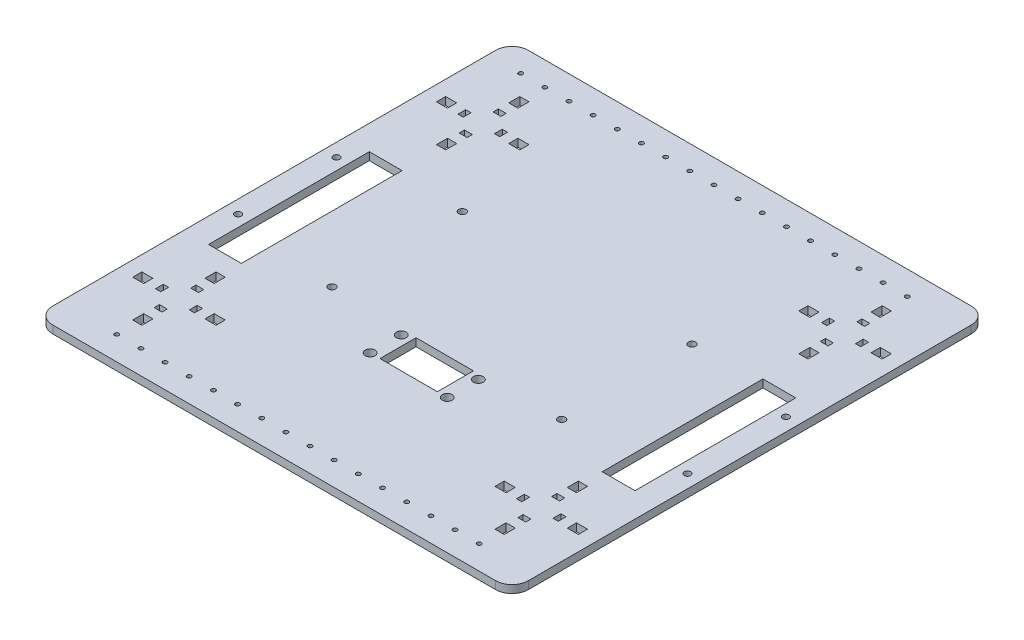
SolidWorks part; units mm, degrees
ref_plane "Front Plane" through (0, 0, 0) normal (0, 0, 1) x (1, 0, 0)
ref_plane "Top Plane" through (0, 0, 0) normal (0, 1, 0) x (1, 0, 0)
ref_plane "Right Plane" through (0, 0, 0) normal (1, 0, 0) x (0, 0, -1)
sketch "Sketch1" plane through (0, 0, 0) normal (0, 1, 0) x (1, 0, 0)
  line L0 (-145, 130.5) -> (145, 130.5) construction
  line L1 (145, -145) -> (-145, -145)
  line L2 (145, -145) -> (145, 145)
  line L3 (145, 145) -> (-145, 145)
  line L4 (-145, -145) -> (-145, 145)
  line L5 (145, -145) -> (-145, 145) construction
  line L6 (145, 145) -> (-145, -145) construction
  line L7 (-145, 116) -> (145, 116) construction
  line L8 (-145, 101.5) -> (145, 101.5) construction
  line L9 (-145, 87) -> (145, 87) construction
  line L10 (-145, 72.5) -> (145, 72.5) construction
  line L11 (-145, 58) -> (145, 58) construction
  line L12 (-145, 43.5) -> (145, 43.5) construction
  line L13 (-145, 29) -> (145, 29) construction
  line L14 (-145, 14.5) -> (145, 14.5) construction
  line L15 (-145, 0) -> (145, 0) construction
  line L16 (-145, -14.5) -> (145, -14.5) construction
  line L17 (-145, -29) -> (145, -29) construction
  line L18 (-145, -43.5) -> (145, -43.5) construction
  line L19 (-145, -58) -> (145, -58) construction
  line L20 (-145, -72.5) -> (145, -72.5) construction
  line L21 (-145, -87) -> (145, -87) construction
  line L22 (-145, -101.5) -> (145, -101.5) construction
  line L23 (-145, -116) -> (145, -116) construction
  line L24 (-145, -130.5) -> (145, -130.5) construction
  line L25 (-145, -145) -> (145, -145) construction
  point P0 (0, 0)
  dimension "D1" = 290
  dimension "D2" = 290
  dimension "D3" = 14.5
  dimension "D5" = 14.5
  dimension "D4" = 20
extrude "Base Plate" add sketch "Sketch1" along normal blind 4.7625
hole_wizard "Caster Holes" positions "Sketch2" profile "Sketch3" hole size "M2" standard "ANSI Metric" end condition through all
sketch "Sketch2" plane through (0, 4.7625, 0) normal (0, 1, 0) x (1, 0, 0)
  line L5 (0, -145) -> (0, 145) construction
  line L6 (145, 145) -> (-145, 145) construction
  line L8 (-145, 0) -> (145, 0) construction
  line L9 (-145, 0) -> (145, 0) construction
  line L10 (-145, 130.5) -> (145, 130.5) construction
  point P200 (-7.366, 130.5)
  point P217 (-22.098, 130.5)
  point P218 (-36.83, 130.5)
  point P219 (-51.562, 130.5)
  point P220 (-66.294, 130.5)
  point P221 (-81.026, 130.5)
  point P222 (-95.758, 130.5)
  point P223 (-110.49, 130.5)
  point P224 (110.49, 130.5)
  point P225 (95.758, 130.5)
  point P226 (81.026, 130.5)
  point P227 (66.294, 130.5)
  point P228 (51.562, 130.5)
  point P229 (36.83, 130.5)
  point P230 (22.098, 130.5)
  point P231 (7.366, 130.5)
  point P232 (7.366, -130.5)
  point P233 (22.098, -130.5)
  point P234 (36.83, -130.5)
  point P235 (51.562, -130.5)
  point P236 (66.294, -130.5)
  point P237 (81.026, -130.5)
  point P238 (95.758, -130.5)
  point P239 (110.49, -130.5)
  point P240 (-110.49, -130.5)
  point P241 (-95.758, -130.5)
  point P242 (-81.026, -130.5)
  point P243 (-66.294, -130.5)
  point P244 (-51.562, -130.5)
  point P245 (-36.83, -130.5)
  point P246 (-22.098, -130.5)
  point P247 (-7.366, -130.5)
  point P250 (-125.222, 130.5)
  dimension "D1" = 7.366
  dimension "D3" = 14.732
  dimension "D2" = 9
sketch "Sketch3" plane through (-125.222, 4.7625, -130.5) normal (1, 0, 0) x (0, 0, 1)
  line L0 (0, 0) -> (0, 4.7625)
  line L1 (0, 4.7625) -> (1.3, 4.7625)
  line L2 (1.3, 4.7625) -> (1.3, 0)
  line L5 (1.3, 0) -> (0, 0)
  line L11 (0, -6.35) -> (0, 107.95) construction
  dimension "Thru Hole Dia." = 2.6
  dimension "Thru Hole Depth" = 4.7625
fillet "Fillet1" radius 10 4 edges at (145, 2.3813, 145) (-145, 2.3813, 145) (145, 2.3813, -145) (-145, 2.3813, -145)
sketch "Sketch4" plane through (0, 0, 0) normal (0, -1, 0) x (1, 0, 0)
  line L0 (145, 0) -> (-145, 0) construction
  line L1 (-145, -135) -> (-145, 135) construction
  line L2 (0, -145) -> (0, 145) construction
  line L3 (-135, 145) -> (135, 145) construction
  point P6 (0, 0)
  point P12 (0, 0)
sketch "Sketch5" plane through (0, 4.7625, 0) normal (0, 1, 0) x (1, 0, 0)
  line L0 (0, 145) -> (0, -145) construction
  line L1 (145, 0) -> (-145, 0) construction
  line L2 (0, 145) -> (0, -145) construction
  line L3 (-17.5, -63) -> (-17.5, -41)
  line L4 (-17.5, -13) -> (17.5, -13) construction
  line L5 (-17.5, -13) -> (-17.5, 9) construction
  line L6 (-17.5, 9) -> (17.5, 9) construction
  line L7 (17.5, -13) -> (17.5, 9) construction
  line L8 (-17.5, -13) -> (17.5, 9) construction
  line L9 (-17.5, 9) -> (17.5, -13) construction
  line L10 (-17.5, -63) -> (17.5, -63)
  line L11 (17.5, -63) -> (17.5, -41)
  line L12 (-17.5, -41) -> (17.5, -41)
  circle A0 centre (-23.5, 6) radius 3 construction
  circle A2 centre (-23.5, -13) radius 3 construction
  circle A3 centre (23.5, 6) radius 3 construction
  circle A4 centre (23.5, -13) radius 3 construction
  circle A5 centre (-23.5, -44) radius 3
  circle A6 centre (-23.5, -63) radius 3
  circle A7 centre (23.5, -63) radius 3
  circle A8 centre (23.5, -44) radius 3
  point P2 (0, -41)
  point P13 (0, -2)
  dimension "D1" = 6
  dimension "D2" = 23.5
  dimension "D3" = 6
  dimension "D4" = 19
  dimension "D5" = 6
  dimension "D6" = 6
  dimension "D8" = 28
  dimension "D7" = 2
extrude "Reflect Holes" cut sketch "Sketch5" against normal up to surface (4.7625 mm away) up to face at (-7.366, 0, -129.2)
sketch "Sketch6" plane through (0, 4.7625, 0) normal (0, 1, 0) x (1, 0, 0)
  line L0 (-137, 145) -> (-137, -145) construction
  line L1 (135, 145) -> (-135, 145) construction
  line L2 (-135, -145) -> (135, -145) construction
  line L3 (-145, 135) -> (-145, -135) construction
  line L16 (145, 0) -> (-145, 0) construction
  line L17 (0, -145) -> (0, 145) construction
  circle A2 centre (-137, 30) radius 2
  circle A22 centre (-137, -30) radius 2
  circle A23 centre (-70, 39.748) radius 2.25
  circle A25 centre (-70, -39.748) radius 2.25
  circle A26 centre (70, -39.748) radius 2.25
  circle A27 centre (70, 39.748) radius 2.25
  circle A28 centre (137, -30) radius 2
  circle A29 centre (137, 30) radius 2
  point P44 (0, 0)
  point P46 (0, 0)
  dimension "D3" = 4
  dimension "D6" = 70
  dimension "D4" = 4.5
  dimension "D1" = 8
  dimension "D2" = 30
  dimension "D5" = 39.748
extrude "bearing slots" cut sketch "Sketch6" against normal up to surface (4.7625 mm away) up to face at (23.5, 0, 47)
sketch "Sketch7" plane through (0, 4.7625, 0) normal (0, 1, 0) x (1, 0, 0)
  line L0 (-145, 135) -> (-145, -135) construction
  line L9 (-130, 43) -> (-110, 43)
  line L10 (-130, 43) -> (-130, -55)
  line L11 (-130, -55) -> (-110, -55)
  line L12 (-110, 43) -> (-110, -55)
  point P9 (-110, -6)
  dimension "D2" = 98
  dimension "D1" = 20
  dimension "D3" = 15
  dimension "D4" = 6
extrude "wheel slots" cut sketch "Sketch7" against normal up to surface (4.7625 mm away) up to face at (-137, 0, 32)
sketch "Sketch9" plane through (0, 4.7625, 0) normal (0, 1, 0) x (1, 0, 0)
  line L0 (-109, -145) -> (-109, 145) construction
  line L1 (135, 145) -> (-135, 145) construction
  line L2 (-145, 135) -> (-145, -135) construction
  line L3 (-135, -145) -> (135, -145) construction
  line L4 (90, -145) -> (90, 145) construction
  line L5 (145, -135) -> (145, 135) construction
  point P0 (-109, -75)
  point P1 (-109, -115)
  point P2 (90, -95)
  point P8 (-109, 0)
  point P21 (90, 0)
  dimension "D1" = 36
  dimension "D2" = 70
  dimension "D3" = 30
  dimension "D4" = 55
  dimension "D5" = 50
sketch "Sketch13" plane through (0, 4.7625, 0) normal (0, 1, 0) x (1, 0, 0)
  line L0 (0, -145) -> (0, 145) construction
  line L7 (135, 145) -> (-135, 145) construction
  line L17 (145, 0) -> (-145, 0) construction
  line L18 (-145, 135) -> (-145, -135) construction
  point P12 (0, 0)
  point P32 (0, 0)
  point P44 (0.04, 0)
mirror "Mirror1" about plane through (0, 0, 0) normal (1, 0, 0) of "wheel slots"
sketch "Sketch15" plane through (0, 4.7625, 0) normal (0, 1, 0) x (1, 0, 0)
  line L21 (-113.25, 118) -> (-107.662, 118)
  line L22 (-113.25, 118) -> (-113.25, 111.269)
  line L23 (-113.25, 111.269) -> (-107.662, 111.269)
  line L24 (-107.662, 118) -> (-107.662, 111.269)
  line L25 (135, 145) -> (-135, 145) construction
  line L26 (-85.056, 95.394) -> (-91.787, 95.394)
  line L27 (-85.056, 95.394) -> (-85.056, 89.806)
  line L28 (-85.056, 89.806) -> (-91.787, 89.806)
  line L29 (-91.787, 95.394) -> (-91.787, 89.806)
  line L30 (-107.662, 67.2) -> (-107.662, 73.931)
  line L31 (-107.662, 67.2) -> (-113.25, 67.2)
  line L32 (-113.25, 67.2) -> (-113.25, 73.931)
  line L33 (-107.662, 73.931) -> (-113.25, 73.931)
  line L34 (-135.856, 89.806) -> (-129.125, 89.806)
  line L35 (-135.856, 89.806) -> (-135.856, 95.394)
  line L36 (-135.856, 95.394) -> (-129.125, 95.394)
  line L37 (-129.125, 89.806) -> (-129.125, 95.394)
  line L38 (-145, 135) -> (-145, -135) construction
  line L39 (-108.4875, 104.925) -> (-113.25, 104.925)
  line L40 (-122.781, 94.5685) -> (-119.581, 94.5685)
  line L41 (-122.781, 94.5685) -> (-122.781, 89.806)
  line L42 (-122.781, 89.806) -> (-119.581, 89.806)
  line L43 (-119.581, 94.5685) -> (-119.581, 89.806)
  line L44 (-108.4875, 104.925) -> (-108.4875, 101.725)
  line L45 (-108.4875, 101.725) -> (-113.25, 101.725)
  line L46 (-113.25, 104.925) -> (-113.25, 101.725)
  line L47 (-98.131, 90.6315) -> (-98.131, 95.394)
  line L48 (-98.131, 90.6315) -> (-101.331, 90.6315)
  line L49 (-101.331, 90.6315) -> (-101.331, 95.394)
  line L50 (-98.131, 95.394) -> (-101.331, 95.394)
  line L51 (-112.4245, 80.275) -> (-107.662, 80.275)
  line L52 (-112.4245, 80.275) -> (-112.4245, 83.475)
  line L53 (-112.4245, 83.475) -> (-107.662, 83.475)
  line L54 (-107.662, 80.275) -> (-107.662, 83.475)
  point P6 (-110.456, 92.6)
  point P10 (-110.456, 111.269)
  point P25 (-110.456, 92.6)
  point P42 (-110.456, 92.6)
  dimension "D1" = 5.588
  dimension "D2" = 6.731
  dimension "D3" = 27
  dimension "D4" = 25.4
  dimension "D6" = 31.75
  dimension "D7" = 3.2
  dimension "D8" = 4.7625
  dimension "D9" = 13.075
  dimension "D5" = 4
  dimension "D10" = 4
extrude "Cut-Extrude2" cut sketch "Sketch15" against normal up to surface (4.7625 mm away) up to face at (-120, 0, 6)
mirror "Mirror2" about plane through (0, 0, 0) normal (1, 0, 0) of "Cut-Extrude2"
mirror "Mirror3" about plane through (0, 0, 0) normal (0, 0, 1) of "Mirror2"
